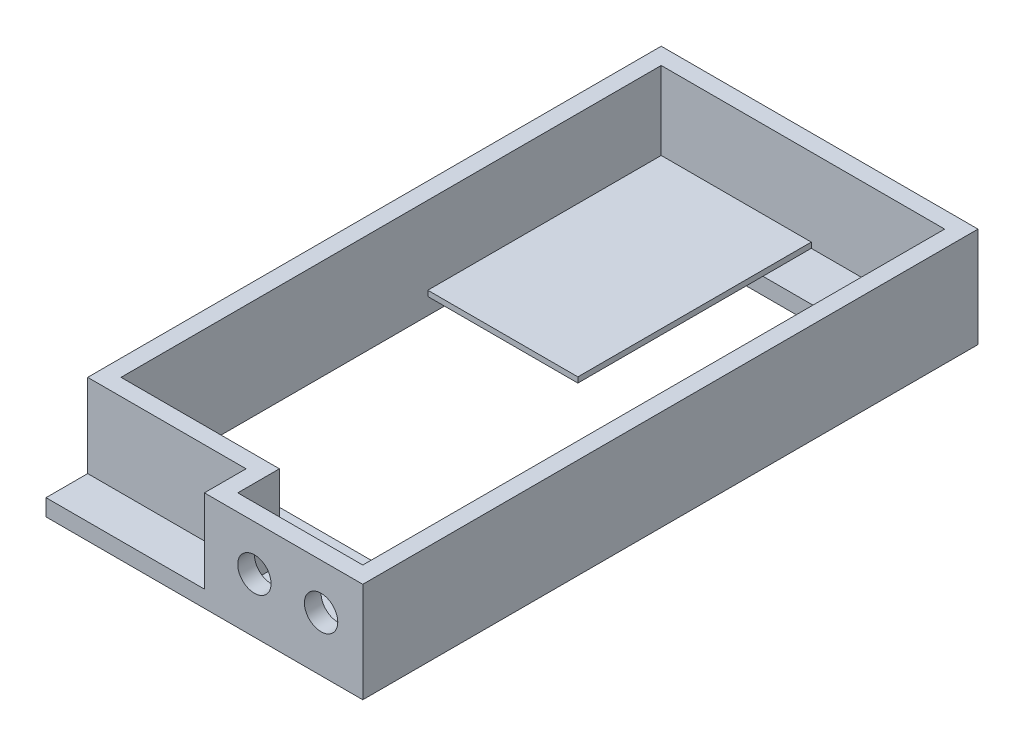
SolidWorks part; units mm, degrees
ref_plane "Front Plane" through (0, 0, 0) normal (0, 0, 1) x (1, 0, 0)
ref_plane "Top Plane" through (0, 0, 0) normal (0, 1, 0) x (1, 0, 0)
ref_plane "Right Plane" through (0, 0, 0) normal (1, 0, 0) x (0, 0, -1)
ref_axis "X-Axis" through (-88.99, 0, 0) along (1, 0, 0)
ref_axis "Y-Axis" through (0, 55, 0) along (0, -1, 0)
ref_axis "Z-Axis" through (0, 0, -88.99) along (0, 0, 1)
sketch "Sketch1" plane through (0, 0, 0) normal (0, 1, 0) x (1, 0, 0)
  line L1 (-19, -36.9) -> (19, -36.9)
  line L2 (-19, -36.9) -> (-19, 36.9)
  line L3 (-19, 36.9) -> (19, 36.9)
  line L4 (19, -36.9) -> (19, 36.9)
  line L5 (-19, -36.9) -> (19, 36.9) construction
  line L6 (-19, 36.9) -> (19, -36.9) construction
  point P0 (0, 0)
  dimension "D1" = 38
  dimension "D2" = 73.8
extrude "Boss-Extrude1" add sketch "Sketch1" along normal blind 12
sketch "Sketch2" plane through (0, 12, 0) normal (0, 1, 0) x (1, 0, 0)
  line L1 (-19, -36.9) -> (0, -36.9)
  line L2 (-19, -36.9) -> (-19, -31.9)
  line L3 (-19, -31.9) -> (0, -31.9)
  line L4 (0, -36.9) -> (0, -31.9)
  dimension "D1" = 5
  dimension "D2" = 19
extrude "Cut-Extrude1" cut sketch "Sketch2" against normal offset from surface (10 mm away) 2 up to face at (0, 0, 0)
sketch "Sketch6" plane through (0, 12, 0) normal (0, 1, 0) x (1, 0, 0)
  line L0 (19, 36.9) -> (-19, 36.9) construction
  line L1 (-4.5, 36.9) -> (0.5, 36.9)
  line L2 (-4.5, 36.9) -> (-4.5, 35.4)
  line L3 (-4.5, 35.4) -> (0.5, 35.4)
  line L4 (0.5, 36.9) -> (0.5, 35.4)
  line L5 (-19, 36.9) -> (-19, -31.9) construction
  dimension "D1" = 5
  dimension "D2" = 1.5
  dimension "D3" = 14.5
extrude "Cut-Extrude4" [suppressed] cut sketch "Sketch6" against normal offset from surface (8 mm away) 4 up to face at (0, 0, 0)
sketch "Sketch7" [suppressed] plane through (0, 12, 0) normal (0, 1, 0) x (1, 0, 0)
  line L0 (-3, 38.5) -> (-3, 37.68) construction
  line L1 (-5.5, 38.5) -> (-0.5, 38.5) construction
  line L3 (-7.1, 36.86) -> (1.1, 36.86)
  line L4 (-7.1, 36.86) -> (-7.1, 38.5)
  line L5 (-7.1, 38.5) -> (1.1, 38.5)
  line L6 (1.1, 36.86) -> (1.1, 38.5)
  line L7 (-7.1, 36.86) -> (1.1, 38.5) construction
  line L8 (-7.1, 38.5) -> (1.1, 36.86) construction
  dimension "D1" = 1.84
  dimension "D2" = 8.2
extrude "Cut-Extrude5" [suppressed] cut sketch "Sketch7" against normal offset from surface (9.6 mm away) 1.6 up to face at (0, 12, 10.6333) offset beyond the face yes
shell "Shell1" thickness 2 removed face at (0, 12, 10.6333)
sketch "Sketch8" [suppressed] plane through (0, 12, 0) normal (0, 1, 0) x (1, 0, 0)
  line L0 (-5.5, 38.5) -> (-5.5, 34.86) construction
  line L1 (-9.1, 34.86) -> (3.1, 34.86) construction
  line L3 (-5.5, 34.86) -> (-0.5, 34.86)
  line L4 (-5.5, 34.86) -> (-5.5, 38.5)
  line L5 (-5.5, 38.5) -> (-0.5, 38.5)
  line L6 (-0.5, 34.86) -> (-0.5, 38.5)
extrude "Cut-Extrude6" [suppressed] cut sketch "Sketch8" against normal up to surface (8 mm away) up to face at (0.6667, 12, 9.9667)
sketch "Sketch9" plane through (0, 0, 36.9) normal (0, 0, 1) x (1, 0, 0)
  line L0 (-19, 0) -> (19, 0) construction
  circle A0 centre (10, 6.5) radius 5
  dimension "D1" = 10
  dimension "D2" = 6.5
  dimension "D3" = 7
extrude "Cut-Extrude7" [suppressed] cut sketch "Sketch9" against normal blind 44 from offset 10 offset against normal yes
sketch "Sketch10" plane through (0, 0, -36.9) normal (0, 0, -1) x (-1, 0, 0)
  line L0 (19, 2.1) -> (8, 2.1) construction
  line L1 (19, 12) -> (19, 0) construction
  line L2 (8, 2.1) -> (8, -1.9) construction
  line L3 (12.25, 2.1) -> (3.75, 2.1)
  line L4 (11.5, -1.9) -> (4.5, -1.9)
  line L5 (3.75, 2.1) -> (4.5, -1.9)
  line L6 (11.5, -1.9) -> (12.25, 2.1)
  line L7 (-19, 0) -> (19, 0) construction
  point P8 (8, 2.1)
  point P10 (8, -1.9)
  dimension "D1" = 4
  dimension "D2" = 7
  dimension "D3" = 8.5
  dimension "D4" = 11
  dimension "D5" = 2.1
extrude "Cut-Extrude8" [suppressed] cut sketch "Sketch10" against normal through all
fillet "Fillet1" [suppressed] radius 0.9
fillet "Fillet2" [suppressed] radius 1
sketch "Sketch11" plane through (0, 2, 0) normal (0, 1, 0) x (1, 0, 0)
  line L1 (-17, 34.9) -> (1, 34.9)
  line L2 (-17, 34.9) -> (-17, 6.9)
  line L3 (-17, 6.9) -> (1, 6.9)
  line L4 (1, 34.9) -> (1, 6.9)
  dimension "D1" = 18
  dimension "D2" = 28
extrude "Boss-Extrude2" add sketch "Sketch11" along normal blind 0.65
sketch "Sketch12" plane through (0, 0, 36.9) normal (0, 0, 1) x (1, 0, 0)
  line L0 (19, 6.5686) -> (0, 6.5686) construction
  line L1 (19, 12) -> (19, 0) construction
  line L2 (0, 2) -> (0, 12) construction
  circle A0 centre (6, 6.5686) radius 2
  circle A1 centre (14, 6.5686) radius 2
  dimension "D1" = 4
  dimension "D2" = 5
  dimension "D3" = 8
extrude "Cut-Extrude9" cut sketch "Sketch12" against normal up to next
sketch "Sketch13" plane through (0, 0, 0) normal (0, -1, 0) x (1, 0, 0)
  line L0 (-19, 36.9) -> (19, 36.9) construction
  line L1 (17, 23.9) -> (-17, 23.9)
  line L2 (17, 23.9) -> (17, -29.1)
  line L3 (17, -29.1) -> (-17, -29.1)
  line L4 (-17, 23.9) -> (-17, -29.1)
  line L6 (-17, 23.9) -> (-19, 23.9) construction
  line L8 (17, 23.9) -> (19, 23.9) construction
  line L9 (19, 36.9) -> (19, -36.9) construction
  line L10 (-19, -36.9) -> (-19, 36.9) construction
  dimension "D1" = 53
  dimension "D2" = 13
  dimension "D4" = 34
extrude "Cut-Extrude10" cut sketch "Sketch13" against normal up to surface (2 mm away) up to face at (0.75, 2, 5.75)
equation "\"D2@Sketch7\"=\"D1@Sketch6\"+(1.6*2)"
equation "\"D2@Sketch9\"=(\"D1@Sketch9\"/2)+\"D1@Cut-Extrude1\"-0.5"
equation "\"D3@Sketch9\"=(\"D1@Sketch9\"/2)+2"
